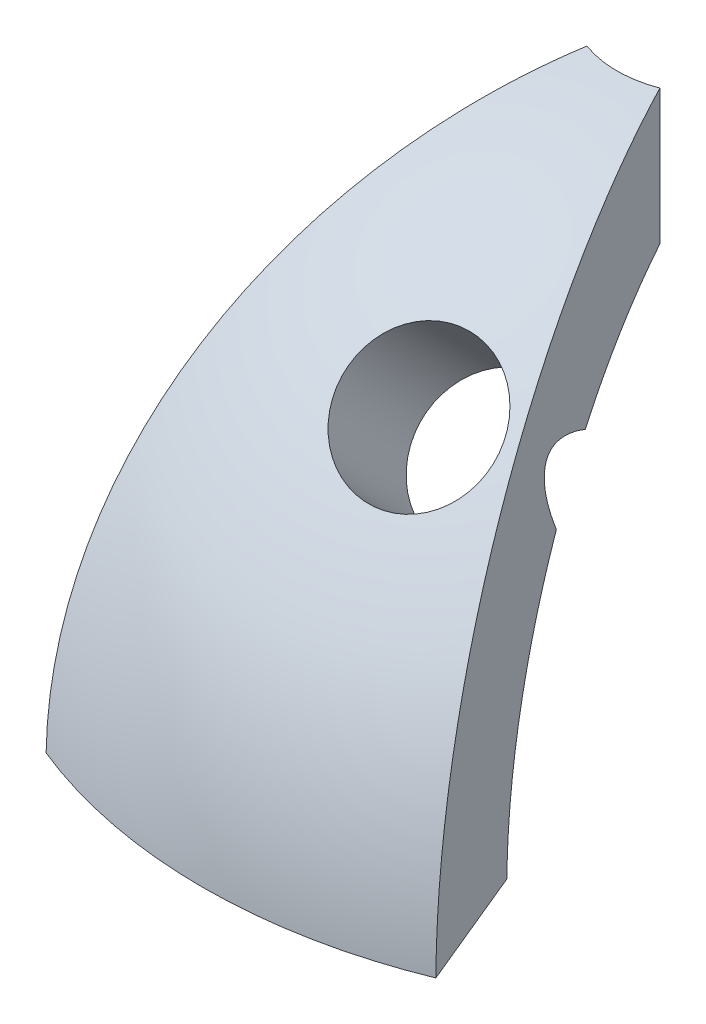
SolidWorks part; units mm, degrees
ref_plane "Front Plane" through (0, 0, 0) normal (0, 0, 1) x (1, 0, 0)
ref_plane "Top Plane" through (0, 0, 0) normal (0, 1, 0) x (1, 0, 0)
ref_plane "Right Plane" through (0, 0, 0) normal (1, 0, 0) x (0, 0, -1)
sketch "Sketch1" plane through (0, 0, 0) normal (1, 0, 0) x (0, 0, -1)
  line L1 (19.05, 0) -> (-19.05, 0) construction
  line L2 (-3.81, 13.4404) -> (-3.81, 9.4186) construction
  line L3 (-14.2178, 0.25) -> (-19.0484, 0.25)
  line L4 (-3.81, 18.6651) -> (-3.81, 13.7001)
  line L5 (0, 0) -> (0, 50000) construction
  arc A0 (-3.81, 13.4404) -> (-13.97, 0) centre (0, 0) ccw construction
  arc A1 (-3.81, 13.4404) -> (-13.97, 0) centre (0, 0) ccw construction
  arc A2 (-3.81, 13.7001) -> (-14.2178, 0.25) centre (0, 0) ccw
  arc A3 (-2.4953, 13.7453) -> (-13.97, 0) centre (0, 0) ccw construction
  arc A4 (-3.81, 18.6651) -> (-19.0484, 0.25) centre (0, 0) ccw
  arc A5 (-2.54, 13.9913) -> (-14.22, 0) centre (0, 0) ccw construction
  arc A6 (-19.05, 0) -> (19.05, 0) centre (0, 0) ccw construction
  dimension "D2" = 0.25
  dimension "D1" = 0.25
revolve "Revolve1" add sketch "Sketch1" angle 45 mid plane about L5
sketch "Sketch2" plane through (0, 0, 0) normal (0, 1, 0) x (1, 0, 0)
  line L0 (7.2895, -17.5984) -> (1.458, -3.52) construction
  line L1 (7.2895, -17.5984) -> (1.458, -3.52)
  line L2 (7.1738, -17.6458) -> (1.3418, -3.5659)
  line L3 (7.174, -17.6462) -> (1.3425, -3.5678) construction
  line L4 (0, 0) -> (0, -50000) construction
  line L5 (-7.1738, -17.6458) -> (-1.3418, -3.5659)
  line L6 (-7.2895, -17.5984) -> (-1.458, -3.52)
  arc A0 (-7.2895, -17.5984) -> (7.2895, -17.5984) centre (0, 0) ccw construction
  arc A1 (-1.458, -3.52) -> (1.458, -3.52) centre (0, 0) ccw construction
  arc A2 (7.1738, -17.6458) -> (7.2895, -17.5984) centre (0, 0) ccw
  arc A3 (1.3418, -3.5659) -> (1.458, -3.52) centre (0, 0) ccw
  arc A4 (-1.3418, -3.5659) -> (-1.458, -3.52) centre (0, 0) cw
  arc A5 (-7.1738, -17.6458) -> (-7.2895, -17.5984) centre (0, 0) cw
  dimension "D1" = 0.125
extrude "Cut-Extrude1" cut sketch "Sketch2" against normal through all both and the other way through all
ref_plane "Plane1" through (0, 0, 0) normal (0, 0.7071, 0.7071) x (-1, 0, 0)
ref_plane "Plane2" through (0, 0, 0) normal (0, 0.3827, 0.9239) x (-1, 0, 0)
sketch "Sketch8" plane through (0, 0, 0) normal (0, 0.3827, 0.9239) x (-1, 0, 0)
  line L0 (-18.6381, 3.9399) -> (18.6381, 3.9399) construction
  arc A0 (19.05, 0) -> (-19.05, 0) centre (0, 0) ccw construction
  ellipse E0 centre (0, -0.231) end of major axis (14.2178, -0.231) minor radius 5.4409 (5.3252, 4.8139) -> (-5.3252, 4.8139) ccw construction
  ellipse E1 centre (0, -0.231) end of major axis (14.2178, -0.231) minor radius 5.4409 (5.3252, 4.8139) -> (-5.3252, 4.8139) ccw construction
  text T0 "<r180>    4</r>" font "Century Gothic" height 4.445
  point P3 (0, 3.9399)
  dimension "D1" = 2.54
extrude "Cut-Extrude4" cut sketch "Sketch8" along normal blind 0.381 from surface starting at face at (0, 7.8389, 9.7254)
ref_plane "Plane3" through (8.5616, 18.8585, 16.8031) normal (0.321, 0.7071, 0.63) x (0.9471, -0.2397, -0.2136)
sketch "Sketch9" plane through (2.9501, 18.8585, 18.6264) normal (-0.1106, -0.7071, -0.6984) x (-0.8917, -0.2397, 0.3839)
  circle A0 centre (0, 0) radius 2.54 construction
  circle A1 centre (0, 0) radius 2.54 construction
  circle A2 centre (0, 0) radius 2.6035
  dimension "D1" = 5.207
extrude "Cut-Extrude5" cut sketch "Sketch9" against normal through all both and the other way through all
